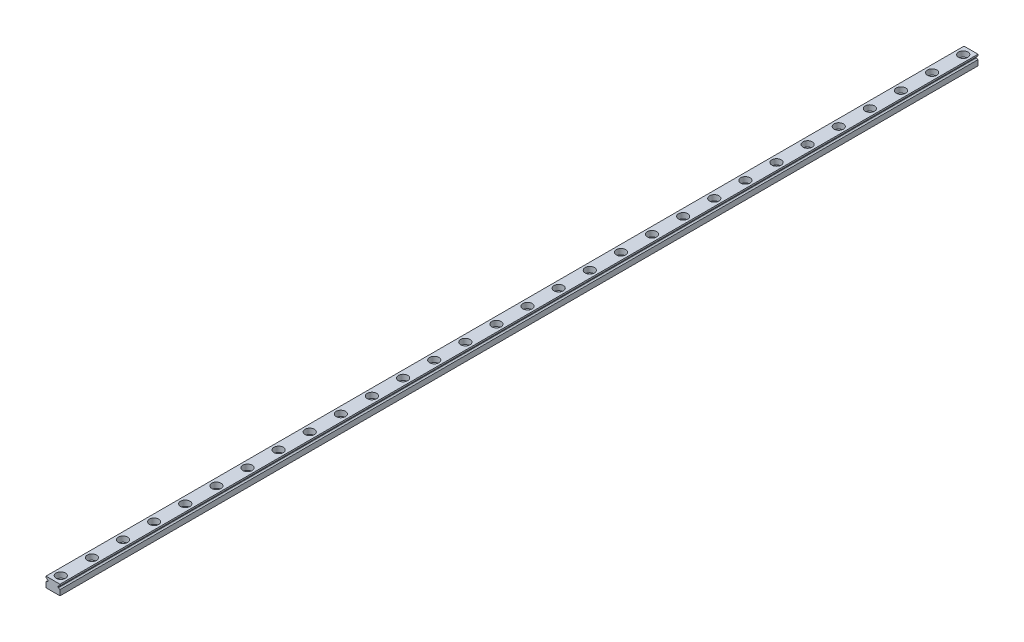
SolidWorks part; units mm, degrees
ref_plane "Front Plane" through (0, 0, 0) normal (0, 0, 1) x (1, 0, 0)
ref_plane "Top Plane" through (0, 0, 0) normal (0, 1, 0) x (1, 0, 0)
ref_plane "Right Plane" through (0, 0, 0) normal (1, 0, 0) x (0, 0, -1)
sketch "Sketch1" plane through (0, 0, 0) normal (0, 0, 1) x (1, 0, 0)
  line L0 (0, 0) -> (0, 5.7299) construction
  line L1 (-4.5, -3.25) -> (4.5, -3.25)
  line L2 (-4.5, -3.25) -> (-4.5, 0.25)
  line L3 (-4.5, 3.25) -> (4.5, 3.25)
  line L4 (4.5, -3.25) -> (4.5, 0.25)
  line L5 (-4.5, -3.25) -> (4.5, 3.25) construction
  line L6 (-4.5, 3.25) -> (4.5, -3.25) construction
  line L7 (-4.5, 2.25) -> (-4.5, 3.25)
  line L8 (-3.564, 0.898) -> (-3.2351, 0.898)
  line L9 (3.564, 0.898) -> (3.2351, 0.898)
  line L10 (-3.564, 1.602) -> (-3.2351, 1.602)
  line L11 (-3.2351, 0.898) -> (-3.2351, 1.602)
  line L12 (3.2351, 0.898) -> (3.2351, 1.602)
  line L13 (3.564, 1.602) -> (3.2351, 1.602)
  line L14 (4.5, 2.25) -> (4.5, 3.25)
  arc A0 (-3.564, 1.602) -> (-4.5, 2.25) centre (-4.5, 1.25) ccw
  arc A1 (-4.5, 0.25) -> (-3.564, 0.898) centre (-4.5, 1.25) ccw
  arc A2 (4.5, 0.25) -> (3.564, 0.898) centre (4.5, 1.25) cw
  arc A3 (3.564, 1.602) -> (4.5, 2.25) centre (4.5, 1.25) cw
  point P0 (0, 0)
  dimension "D3" = 1
  dimension "D1" = 9
  dimension "D2" = 6.5
  dimension "D4" = 2
extrude "Extrude1" add sketch "Sketch1" along normal blind 590
sketch "Sketch2" plane through (0, 3.25, 0) normal (0, 1, 0) x (1, 0, 0)
  line L0 (4.5, 0) -> (-4.5, 0) construction
  circle A0 centre (0, -5) radius 1.75
  circle A1 centre (0, -5) radius 3
  dimension "D1" = 3.5
  dimension "D2" = 6
  dimension "D3" = 5
extrude "Extrude2" cut sketch "Sketch2" against normal blind 3.5 contours A1
extrude "Extrude3" cut sketch "Sketch" against normal through all contours A0
sketch "Sketch" plane through (0, 3.25, 0) normal (0, 1, 0) x (1, 0, 0) same geometry as "Sketch2"
pattern_linear "LPattern1" count 30 spacing 20 along (0, 0, 1) of "Extrude2", "Extrude3"
